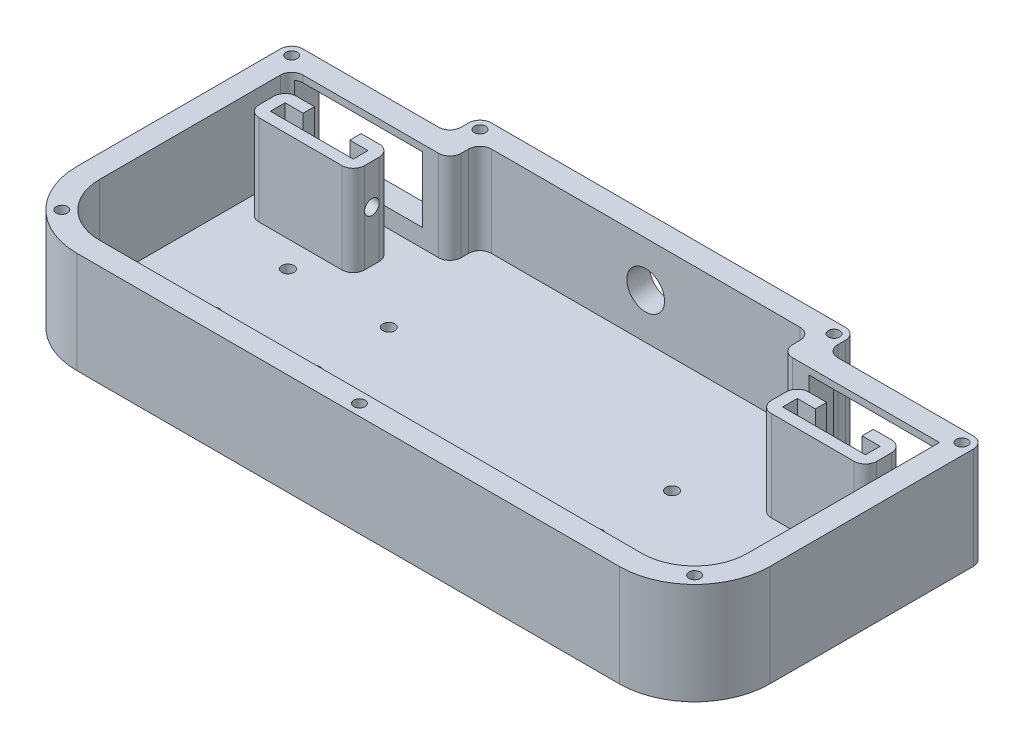
SolidWorks part; units mm, degrees
ref_plane "Front Plane" through (0, 0, 0) normal (0, 0, 1) x (1, 0, 0)
ref_plane "Top Plane" through (0, 0, 0) normal (0, 1, 0) x (1, 0, 0)
ref_plane "Right Plane" through (0, 0, 0) normal (1, 0, 0) x (0, 0, -1)
sketch "Sketch1" plane through (0, 0, 0) normal (0, 1, 0) x (1, 0, 0)
  line L0 (50, 42.5) -> (92, 42.5) construction
  line L31 (-92, -42.5) -> (92, -42.5)
  line L32 (-92, -42.5) -> (-92, 34.5)
  line L121 (-50, 42.5) -> (50, 42.5)
  line L122 (92, -42.5) -> (92, 34.5)
  line L123 (-92, -42.5) -> (92, 42.5) construction
  line L124 (-92, 42.5) -> (92, -42.5) construction
  line L127 (92, 34.5) -> (50, 34.5)
  line L128 (50, 42.5) -> (50, 34.5)
  line L129 (92, 42.5) -> (92, 34.5) construction
  line L130 (-92, 34.5) -> (-92, 42.5) construction
  line L133 (-92, 34.5) -> (-50, 34.5)
  line L134 (-50, 42.5) -> (-50, 34.5)
  line L135 (-92, 42.5) -> (-50, 42.5) construction
  line L137 (-67, 9.5) -> (-33, 9.5) construction
  line L138 (-33, 9.5) -> (-33, -17.5) construction
  line L139 (-33, -17.5) -> (-67, -17.5) construction
  line L140 (-67, -17.5) -> (-67, 9.5) construction
  line L144 (-67, -4) -> (-33, -4) construction
  line L145 (-86, -36.5) -> (-86, 28.5)
  line L146 (-86, 28.5) -> (-44, 28.5)
  line L147 (-44, 36.5) -> (-44, 28.5)
  line L148 (-44, 36.5) -> (44, 36.5)
  line L149 (44, 36.5) -> (44, 28.5)
  line L150 (86, 28.5) -> (44, 28.5)
  line L151 (86, -36.5) -> (86, 28.5)
  line L152 (-86, -36.5) -> (86, -36.5)
  line L155 (-67, -4) -> (-86, -4) construction
  line L156 (0, 36.5) -> (0, -36.5) construction
  line L160 (-50, 28.5) -> (-50, 9.5) construction
  line L161 (51.5, 38.5) -> (84.5, 38.5) construction
  line L162 (84.5, 38.5) -> (84.5, 27.5) construction
  line L163 (84.5, 27.5) -> (51.5, 27.5) construction
  line L164 (51.5, 27.5) -> (51.5, 38.5) construction
  line L165 (58, 19.55) -> (58, 16.05) construction
  line L166 (58, 16.05) -> (78, 16.05) construction
  line L167 (78, 16.05) -> (78, 19.55) construction
  line L168 (68, 27.5) -> (68, 19.55) construction
  line L169 (58, 19.55) -> (78, 19.55) construction
  line L170 (62, 27.5) -> (62, 19.55) construction
  line L171 (74, 27.5) -> (74, 19.55) construction
  line L172 (68, 19.55) -> (68, 16.05) construction
  line L173 (-57, 15.85) -> (-54, 19.75) construction
  line L174 (61.8, 19.75) -> (54, 19.75)
  line L175 (61.8, 19.75) -> (61.8, 22.75)
  line L176 (61.8, 22.75) -> (54, 22.75)
  line L177 (54, 19.75) -> (54, 22.75)
  line L178 (61.8, 19.75) -> (54, 22.75) construction
  line L179 (61.8, 22.75) -> (54, 19.75) construction
  line L180 (74.2, 19.75) -> (82, 19.75)
  line L181 (74.2, 19.75) -> (74.2, 22.75)
  line L182 (74.2, 22.75) -> (82, 22.75)
  line L183 (82, 19.75) -> (82, 22.75)
  line L184 (74.2, 19.75) -> (82, 22.75) construction
  line L185 (74.2, 22.75) -> (82, 19.75) construction
  line L186 (82, 19.75) -> (79, 19.75)
  line L187 (82, 19.75) -> (82, 12.85)
  line L188 (82, 12.85) -> (79, 12.85)
  line L189 (79, 19.75) -> (79, 12.85)
  line L190 (82, 19.75) -> (79, 12.85) construction
  line L191 (82, 12.85) -> (79, 19.75) construction
  line L192 (79, 12.85) -> (54, 12.85)
  line L193 (79, 12.85) -> (79, 15.85)
  line L194 (79, 15.85) -> (54, 15.85)
  line L195 (54, 12.85) -> (54, 15.85)
  line L196 (79, 12.85) -> (54, 15.85) construction
  line L197 (79, 15.85) -> (54, 12.85) construction
  line L198 (57, 19.75) -> (54, 19.75)
  line L199 (57, 19.75) -> (57, 15.85)
  line L200 (57, 15.85) -> (54, 15.85)
  line L201 (54, 19.75) -> (54, 15.85)
  line L202 (57, 19.75) -> (54, 15.85) construction
  line L203 (57, 15.85) -> (54, 19.75) construction
  line L204 (-57, 19.75) -> (-54, 15.85) construction
  line L205 (-79, 15.85) -> (-54, 12.85) construction
  line L206 (-79, 12.85) -> (-54, 15.85) construction
  line L207 (-82, 12.85) -> (-79, 19.75) construction
  line L208 (-82, 19.75) -> (-79, 12.85) construction
  line L209 (-74.2, 22.75) -> (-82, 19.75) construction
  line L210 (-74.2, 19.75) -> (-82, 22.75) construction
  line L211 (-61.8, 22.75) -> (-54, 19.75) construction
  line L212 (-61.8, 19.75) -> (-54, 22.75) construction
  line L213 (-68, 19.55) -> (-68, 16.05) construction
  line L214 (-54, 19.75) -> (-54, 15.85)
  line L215 (-57, 15.85) -> (-54, 15.85)
  line L216 (-57, 19.75) -> (-57, 15.85)
  line L217 (-57, 19.75) -> (-54, 19.75)
  line L218 (-54, 12.85) -> (-54, 15.85)
  line L219 (-79, 15.85) -> (-54, 15.85)
  line L220 (-79, 12.85) -> (-79, 15.85)
  line L221 (-79, 12.85) -> (-54, 12.85)
  line L222 (-79, 19.75) -> (-79, 12.85)
  line L223 (-82, 12.85) -> (-79, 12.85)
  line L224 (-82, 19.75) -> (-82, 12.85)
  line L225 (-82, 19.75) -> (-79, 19.75)
  line L226 (-82, 19.75) -> (-82, 22.75)
  line L227 (-74.2, 22.75) -> (-82, 22.75)
  line L228 (-74.2, 19.75) -> (-74.2, 22.75)
  line L229 (-74.2, 19.75) -> (-82, 19.75)
  line L230 (-54, 19.75) -> (-54, 22.75)
  line L231 (-61.8, 22.75) -> (-54, 22.75)
  line L232 (-61.8, 19.75) -> (-61.8, 22.75)
  line L233 (-61.8, 19.75) -> (-54, 19.75)
  line L234 (67, -4) -> (33, -4) construction
  line L235 (67, -17.5) -> (67, 9.5) construction
  line L236 (33, -17.5) -> (67, -17.5) construction
  line L237 (33, 9.5) -> (33, -17.5) construction
  line L238 (67, 9.5) -> (33, 9.5) construction
  line L239 (-86, 28.5) -> (-92, 34.5) construction
  line L240 (-81.8995, -32.3995) -> (-86.1421, -36.6421) construction
  line L241 (-50, 42.5) -> (-44, 36.5) construction
  line L242 (0, -36.5) -> (0, -42.5) construction
  line L243 (-92, -22.5) -> (-86, -22.5) construction
  line L244 (-72, -36.5) -> (-72, -42.5) construction
  circle A0 centre (-37.6, 5.9) radius 1.6
  circle A1 centre (-64.4, 5.9) radius 1.6
  circle A2 centre (-64.4, -13.9) radius 1.6
  circle A3 centre (-37.6, -13.9) radius 1.6
  circle A4 centre (37.6, -13.9) radius 1.6
  circle A5 centre (64.4, -13.9) radius 1.6
  circle A6 centre (64.4, 5.9) radius 1.6
  circle A7 centre (37.6, 5.9) radius 1.6
  circle A8 centre (-89, 31.5) radius 1.5
  circle A10 centre (-47, 39.5) radius 1.5
  circle A11 centre (0, -39.5) radius 1.5
  circle A13 centre (89, 31.5) radius 1.5
  circle A14 centre (47, 39.5) radius 1.5
  arc A18 (-86, -22.5) -> (-72, -36.5) centre (-72, -22.5) ccw
  circle A19 centre (-84.0208, -34.5208) radius 1.5
  arc A20 (92, -22.5) -> (72, -42.5) centre (72, -22.5) cw
  circle A21 centre (84.0208, -34.5208) radius 1.5
  arc A22 (86, -22.5) -> (72, -36.5) centre (72, -22.5) cw
  arc A23 (-92, -22.5) -> (-72, -42.5) centre (-72, -22.5) ccw
  point P0 (0, 0)
  point P38 (0, 0)
  point P60 (57.9, 21.25)
  point P63 (78.1, 21.25)
  point P68 (80.5, 16.3)
  point P72 (66.5, 14.35)
  point P74 (80.5, 19.75)
  point P76 (55.5, 17.8)
  point P95 (-55.5, 17.8)
  point P96 (-66.5, 14.35)
  point P97 (-80.5, 16.3)
  point P98 (-78.1, 21.25)
  point P99 (-57.9, 21.25)
  dimension "D5" = 42
  dimension "D6" = 8
  dimension "D7" = 34
  dimension "D8" = 27
  dimension "D18" = 11
  dimension "D19" = 11.45
  dimension "D20" = 20
  dimension "D21" = 3.5
  dimension "D32" = 3
  dimension "D24" = 1.5
  dimension "D13" = 3.2
  dimension "D14" = 3.2
  dimension "D38" = 3
  dimension "D39" = 3
  dimension "D41" = 3
  dimension "D1" = 184
  dimension "D2" = 85
  dimension "D3" = 42
  dimension "D4" = 8
  dimension "D9" = 3.6
  dimension "D10" = 3.6
  dimension "D11" = 4.6
  dimension "D12" = 2.6
  dimension "D15" = 6
  dimension "D16" = 36
  dimension "D17" = 33
  dimension "D22" = 12
  dimension "D23" = 6
  dimension "D25" = 4
  dimension "D26" = 0.2
  dimension "D27" = 0.2
  dimension "D28" = 1
  dimension "D29" = 1
  dimension "D30" = 0.2
  dimension "D31" = 0.2
  dimension "D33" = 3
  dimension "D34" = 3
  dimension "D35" = 3
  dimension "D36" = 3
  dimension "D37" = 0.2
  dimension "D42" = 20
  dimension "D43" = 20
extrude "Boss-Extrude1" add sketch "Sketch1" along normal blind 3 contours L121 L134 L133 L32 L31 L122 L127 L128 A13 L152 L145 L146 L147 L148 L149 L150 L151 A8 A10 A11 A14 | A8 | A11 | A13 | A14 | A10 | L148 L149 L150 L151 L152 L145 L146 L147 region at (-89.9732, 0, -6) region at (-89, 0, -31.5) region at (-47, 0, -39.5) region at (0, 0, 39.5) region at (89, 0, -31.5) region at (47, 0, -39.5)
extrude "Boss-Extrude2" add sketch "Sketch1<9>" along normal blind 27 contours L121 L134 L133 L32 L31 L122 L127 L128 A13 L152 L145 L146 L147 L148 L149 L150 L151 A8 A10 A11 A14 | L232 L233 L217 L230 L231 | L217 L216 L215 L214 | L220 L221 L218 L215 L219 | L229 L228 L227 L226 L225 | L225 L224 L223 L220 L222 | L177 L174 L175 L176 | L174 L201 L194 L199 | L195 L192 L189 L194 | L180 L183 L182 L181 | L180 L189 L188 L187 | A18 L145 L152 A19 | L151 A22 L152 A21 region at (-89.9732, 0, -6) region at (-82.641, 0, 33.141) region at (82.641, 0, 33.141) region at (57.9, 0, -21.25) region at (55.5, 0, -17.8) region at (66.5, 0, -14.35) region at (80.5, 0, -16.3) region at (78.1, 0, -21.25) region at (-55.5, 0, -17.8) region at (-57.9, 0, -21.25) region at (-66.5, 0, -14.35) region at (-80.5, 0, -16.3) region at (-78.1, 0, -21.25)
sketch "Sketch1<9>" plane through (0, 0, 0) normal (0, 1, 0) x (1, 0, 0) same geometry as "Sketch1"
sketch "Sketch2" plane through (0, 3, 0) normal (0, 1, 0) x (1, 0, 0)
  line L1 (-79, 15.85) -> (-57, 15.85)
  line L2 (-79, 15.85) -> (-79, 19.75)
  line L3 (-79, 19.75) -> (-57, 19.75)
  line L4 (-57, 15.85) -> (-57, 19.75)
  line L5 (-79, 15.85) -> (-57, 19.75) construction
  line L6 (-79, 19.75) -> (-57, 15.85) construction
  line L7 (57, 15.85) -> (79, 15.85)
  line L8 (57, 15.85) -> (57, 19.75)
  line L9 (57, 19.75) -> (79, 19.75)
  line L10 (79, 15.85) -> (79, 19.75)
  line L11 (57, 15.85) -> (79, 19.75) construction
  line L12 (57, 19.75) -> (79, 15.85) construction
  point P4 (-68, 17.8)
  point P11 (68, 17.8)
extrude "Boss-Extrude3" add sketch "Sketch2" along normal blind 2.5
sketch "Sketch5" plane through (0, 27, 0) normal (0, 1, 0) x (1, 0, 0)
  line L0 (-79, 19.75) -> (-82, 19.75) construction
  line L1 (-82, 12.85) -> (-82, 22.75) construction
  line L2 (-79, 15.85) -> (-82, 15.85) construction
sketch "Sketch6" plane through (-82, 0, 0) normal (-1, 0, 0) x (0, 0, 1)
  line L0 (-12.85, 3) -> (-22.75, 3) construction
  line L2 (-19.75, 27) -> (-15.85, 27)
  line L3 (-19.75, 27) -> (-19.75, 5.5)
  line L4 (-19.75, 5.5) -> (-15.85, 5.5)
  line L5 (-15.85, 27) -> (-15.85, 5.5)
  circle A0 centre (-17.8, 16.5) radius 1.95
  dimension "D1" = 2.5
  dimension "D2" = 11
extrude "Cut-Extrude1" cut sketch "Sketch6" against normal up to surface (164 mm away) contours A0 region at (-82, 16.5, -17.8) up to face at (82, 15, -17.8)
extrude "Cut-Extrude7" cut sketch "Sketch1<12>" along normal through all contours A2 | A3 | A6 | A7 | A5 | A4 | A1 | A0 region at (-64.4, 0, 13.9) region at (-37.6, 0, 13.9) region at (37.6, 0, 13.9) region at (64.4, 0, 13.9) region at (64.4, 0, -5.9) region at (37.6, 0, -5.9)
sketch "Sketch1<12>" plane through (0, 0, 0) normal (0, 1, 0) x (1, 0, 0) same geometry as "Sketch1"
sketch "Sketch7" plane through (0, 0, -42.5) normal (0, 0, -1) x (-1, 0, 0)
  line L0 (0, 0) -> (0, 3) construction
  line L3 (0, 3) -> (0, 27) construction
  line L4 (50, 27) -> (-50, 27) construction
  circle A0 centre (0, 15) radius 5
  dimension "D2" = 10
  dimension "D1" = 3
extrude "Cut-Extrude8" cut sketch "Sketch7" against normal blind 10
fillet "Fillet1" radius 3 11 edges at (-86, 15, -28.5) (-92, 13.5, -34.5) (-50, 13.5, -34.5) (-50, 13.5, -42.5) (-44, 15, -36.5) (-44, 15, -28.5) (44, 15, -28.5) (92, 13.5, -34.5) (50, 13.5, -42.5) (50, 13.5, -34.5) (44, 15, -36.5)
fillet "Fillet2" radius 3 8 edges at (-82, 15, -22.75) (-82, 15, -12.85) (-54, 15, -12.85) (-54, 15, -22.75) (54, 15, -22.75) (54, 15, -12.85) (82, 15, -22.75) (82, 15, -12.85)
sketch "Sketch8" plane through (-92, 0, 0) normal (-1, 0, 0) x (0, 0, 1)
  line L0 (-36.6, 25) -> (-25.6, 25) construction
  line L1 (-25.6, 25) -> (-25.6, 8) construction
  line L2 (-25.6, 8) -> (-36.6, 8) construction
  line L3 (-36.6, 8) -> (-36.6, 25) construction
  line L4 (-15.85, 27) -> (-15.85, 0) construction
  line L5 (22.5, 0) -> (-31.5, 0) construction
  line L6 (-25.6, 16.5) -> (-15.85, 16.5) construction
  line L7 (-15.85, 5.5) -> (-20.9254, 5.5) construction
  line L8 (-36.8, 25.2) -> (-25.4, 25.2)
  line L9 (-25.4, 25.2) -> (-25.4, 7.8)
  line L10 (-25.4, 7.8) -> (-36.8, 7.8)
  line L11 (-36.8, 7.8) -> (-36.8, 25.2)
  dimension "D1" = 17
  dimension "D2" = 11
  dimension "D3" = 9.75
  dimension "D4" = 5.5
  dimension "D5" = 11
  dimension "D6" = 0.2
sketch "Sketch9" plane through (0, 27, 0) normal (0, 1, 0) x (1, 0, 0)
  line L0 (-79, 15.85) -> (-92, 15.85) construction
  line L1 (-92, -22.5) -> (-92, 31.5) construction
extrude "Cut-Extrude9" cut sketch "Sketch8" against normal blind 33.4 from offset 7.3 offset against normal yes
mirror "Mirror1" about plane through (0, 0, 0) normal (1, 0, 0) of "Cut-Extrude9"
